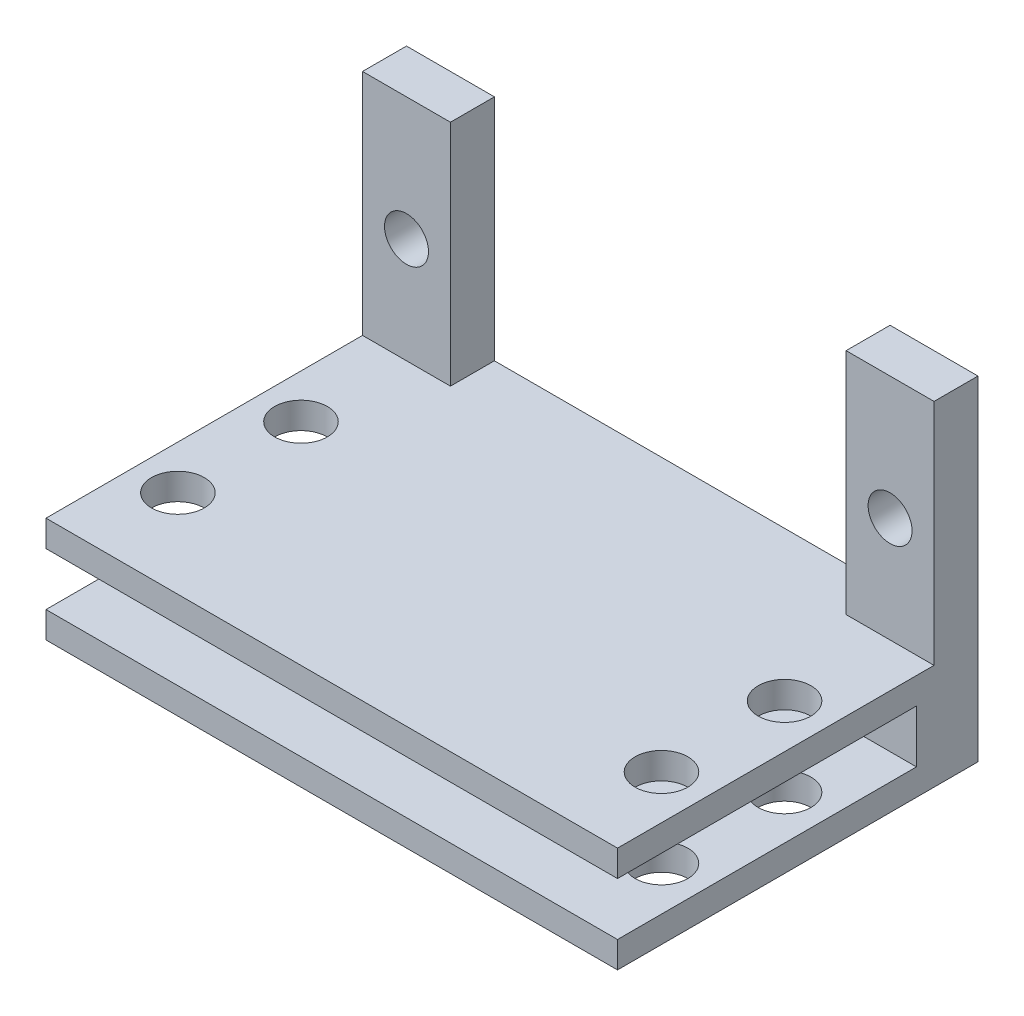
SolidWorks part; units mm, degrees
ref_plane "Front Plane" through (0, 0, 0) normal (0, 0, 1) x (1, 0, 0)
ref_plane "Top Plane" through (0, 0, 0) normal (0, 1, 0) x (1, 0, 0)
ref_plane "Right Plane" through (0, 0, 0) normal (1, 0, 0) x (0, 0, -1)
sketch "Sketch1" plane through (0, 0, 0) normal (0, 0, 1) x (1, 0, 0)
  line L0 (-16.25, 0) -> (-11.25, 0)
  line L1 (-16.25, 0) -> (-16.25, 13)
  line L2 (-16.25, 13) -> (-11.25, 13)
  line L3 (-11.25, 0) -> (-11.25, 13)
  line L8 (0, 12.0231) -> (0, -13.0504) construction
  line L9 (-16.25, 0) -> (16.25, 0)
  line L10 (-16.25, 0) -> (-16.25, -6)
  line L11 (-16.25, -6) -> (16.25, -6)
  line L13 (-16.25, -1.5) -> (16.25, -1.5)
  line L14 (-16.25, -1.5) -> (-16.25, -4.5)
  line L15 (-16.25, -4.5) -> (16.25, -4.5)
  line L17 (16.25, -1.5) -> (16.25, -4.5)
  line L18 (16.25, 0) -> (16.25, -6)
  line L19 (11.25, 0) -> (11.25, 13)
  line L20 (16.25, 13) -> (11.25, 13)
  line L21 (16.25, 0) -> (16.25, 13)
  line L22 (16.25, 0) -> (11.25, 0)
  circle A0 centre (-13.75, 6) radius 1.25
  circle A1 centre (13.75, 6) radius 1.25
  point P10 (13.75, 6)
  point P17 (0, -6)
  point P18 (0, 0)
  dimension "D7" = 6
  dimension "D8" = 2.5
  dimension "D1" = 6
  dimension "D2" = 1.5
  dimension "D3" = 5
  dimension "D4" = 13
  dimension "D5" = 1.5
  dimension "D6" = 11.25
  dimension "D9" = 2.5
extrude "Boss-Extrude1" add sketch "Sketch1" along normal blind 2.5 contours L0 L3 L2 L1 A0 | L9 L21 L20 L19 A1 region at (-16.1107, 6.5, 0) region at (11.3893, 6.5, 0)
extrude "Boss-Extrude2" add sketch "Sketch1<5>" along normal blind 20.5 contours L8 L9 L0 L10 L13 | L9 L8 L13 L18 | L8 L15 L10 L11 | L15 L8 L11 L18 region at (-8.125, -0.75, 0) region at (8.125, -0.75, 0) region at (-8.125, -5.25, 0) region at (8.125, -5.25, 0)
sketch "Sketch1<5>" plane through (0, 0, 0) normal (0, 0, 1) x (1, 0, 0) same geometry as "Sketch1"
extrude "Boss-Extrude3" add sketch "Sketch1<6>" along normal blind 3.5 contours L8 L13 L10 L15 | L13 L8 L15 L17 region at (-8.125, -3, 0) region at (8.125, -3, 0)
sketch "Sketch1<6>" plane through (0, 0, 0) normal (0, 0, 1) x (1, 0, 0) same geometry as "Sketch1"
sketch "Sketch2" plane through (0, 0, 0) normal (0, 1, 0) x (1, 0, 0)
  line L0 (0, -27.4164) -> (0, 3.5034) construction
  line L2 (16.25, -20.5) -> (16.25, -2.5) construction
  line L3 (-16.25, -20.5) -> (16.25, -20.5) construction
  circle A0 centre (13.75, -8.5) radius 1.5
  circle A1 centre (13.75, -15.5) radius 1.5
  circle A2 centre (-13.75, -15.5) radius 1.5
  circle A3 centre (-13.75, -8.5) radius 1.5
  point P6 (0, 0)
  point P8 (11.7642, -20.3555)
  dimension "D1" = 3
  dimension "D2" = 3
  dimension "D3" = 7
  dimension "D4" = 5
  dimension "D5" = 2.5
extrude "Cut-Extrude2" cut sketch "Sketch2" against normal through all both and the other way through all
